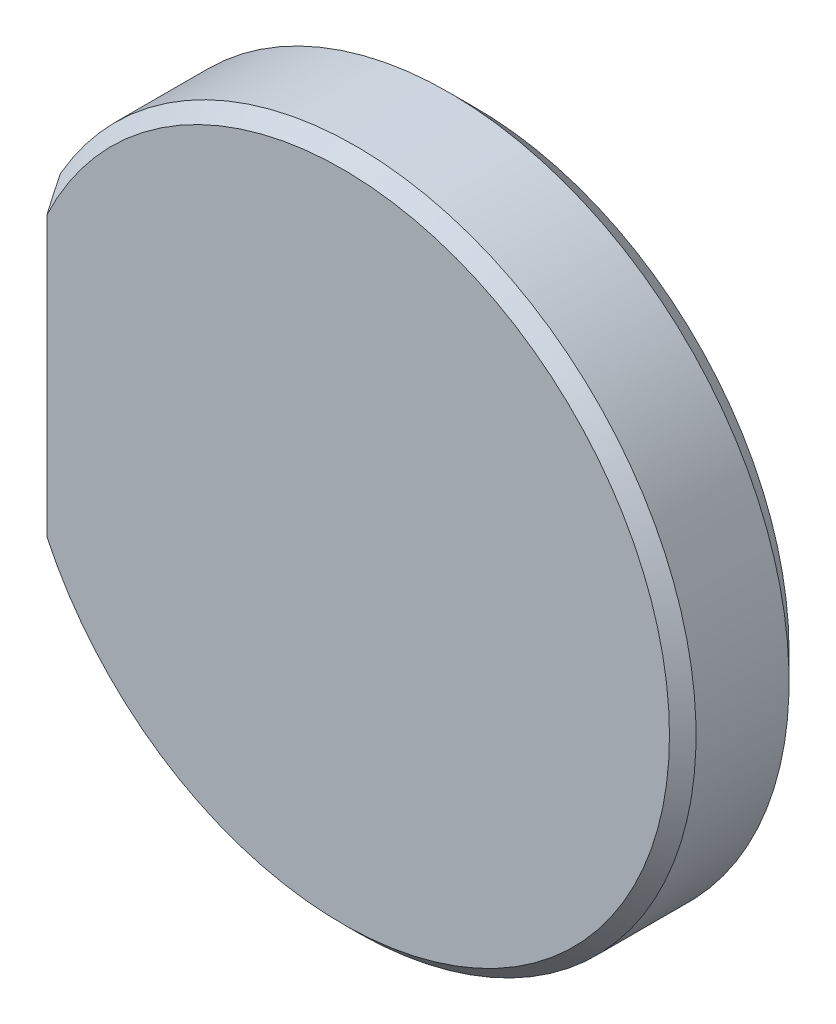
SolidWorks part; units mm, degrees
material "Сплав 2024"
ref_plane "Спереди" through (0, 0, 0) normal (0, 0, 1) x (1, 0, 0)
ref_plane "Сверху" through (0, 0, 0) normal (0, 1, 0) x (1, 0, 0)
ref_plane "Справа" through (0, 0, 0) normal (1, 0, 0) x (0, 0, -1)
sketch "Эскиз1" plane through (0, 0, 0) normal (0, 0, 1) x (1, 0, 0)
  circle A0 centre (0, 0) radius 25.6
  dimension "D1" = 51.2
extrude "Бобышка-Вытянуть1" add sketch "Эскиз1" along normal blind 10
chamfer "Фаска1" distance 2 angle 45 1 edges at (25.6, 0, 0)
sketch "Эскиз2" plane through (0, 0, 10) normal (0, 0, 1) x (1, 0, 0)
  line L0 (-22.25, -12.6609) -> (-22.25, 12.6609)
  line L1 (-22.25, -12.5) -> (-22.25, -10) construction
  circle A0 centre (0, 0) radius 25.6 construction
  arc A1 (-22.25, 12.6609) -> (-22.25, -12.6609) centre (0, 0) ccw
  circle A2 centre (0, 0) radius 25.6 construction
extrude "Вырез-Вытянуть1" cut sketch "Эскиз2" against normal blind 2.5
sketch "Эскиз3" plane through (0, 0, 0) normal (0, 0, -1) x (-1, 0, 0)
  circle A0 centre (0, 0) radius 23.2
  dimension "D1" = 46.4
extrude "Вырез-Вытянуть2" cut sketch "Эскиз3" against normal offset from surface (7.5 mm away) 2.5 up to face at (1.675, 0, 10)
ref_plane "Плоскость1" through (0, -12.6609, 0) normal (0, 1, 0) x (1, 0, 0)
sketch "Эскиз5" plane through (0, 0, 0) normal (0, 0, -1) x (-1, 0, 0)
  line L0 (22.25, 6.571) -> (22.25, -6.571) construction
  line L1 (17.5672, 12.6609) -> (26.9328, 12.6609)
  line L2 (17.5672, 12.6609) -> (17.5672, -12.6609)
  line L3 (17.5672, -12.6609) -> (26.9328, -12.6609)
  line L4 (26.9328, 12.6609) -> (26.9328, -12.6609)
  line L5 (17.5672, 12.6609) -> (26.9328, -12.6609) construction
  line L6 (17.5672, -12.6609) -> (26.9328, 12.6609) construction
  line L7 (1.375, -12.6609) -> (-1.375, -12.6609) construction
  point P0 (22.25, 0)
extrude "Вырез-Вытянуть3" cut sketch "Эскиз5" against normal up to surface (7.5 mm away) up to face at (0.475, 0, 7.5)
fillet "Скругление2" radius 4 2 edges at (-19.4407, 12.6609, 3.75) (-19.4407, -12.6609, 3.75)
chamfer "Фаска2" distance 1 angle 45 1 edges at (25.6, 0, 10)
